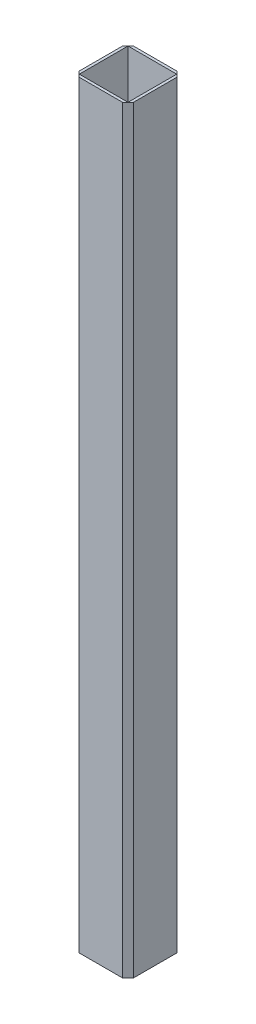
SolidWorks part; units mm, degrees
ref_plane "Front Plane" through (0, 0, 0) normal (0, 0, 1) x (1, 0, 0)
ref_plane "Top Plane" through (0, 0, 0) normal (0, 1, 0) x (1, 0, 0)
ref_plane "Right Plane" through (0, 0, 0) normal (1, 0, 0) x (0, 0, -1)
sketch "Sketch1" plane through (0, 0, 0) normal (0, 0, 1) x (1, 0, 0)
  line L1 (0, 0) -> (50, 0)
  line L2 (0, 0) -> (0, 700)
  line L3 (0, 700) -> (50, 700)
  line L4 (50, 0) -> (50, 700)
  dimension "D1" = 50
  dimension "D2" = 700
extrude "Boss-Extrude1" add sketch "Sketch1" along normal blind 50
sketch "Sketch2" plane through (0, 700, 0) normal (0, 1, 0) x (1, 0, 0)
  line L1 (50, 0) -> (0, 0) construction
  line L3 (2.5, -2.5) -> (47.5, -2.5)
  line L4 (47.5, -2.5) -> (47.5, -47.5)
  line L5 (47.5, -47.5) -> (2.5, -47.5)
  line L6 (2.5, -47.5) -> (2.5, -2.5)
  line L7 (50, -50) -> (50, 0) construction
  line L8 (50, -50) -> (0, -50) construction
  line L9 (0, -50) -> (0, 0) construction
  dimension "D1" = 2.5
  dimension "D2" = 2.5
  dimension "D3" = 2.5
  dimension "D4" = 2.5
extrude "Cut-Extrude1" cut sketch "Sketch2" against normal through all contours L3 L4 L5 L6
chamfer "Chamfer5" distance 5 angle 45 4 edges at (0, 350, 50) (0, 350, 0) (50, 350, 50) (50, 350, 0)
